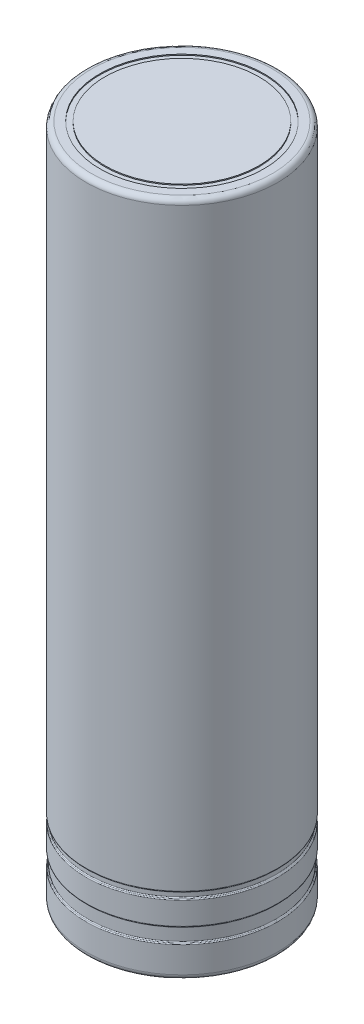
SolidWorks part; units mm, degrees
ref_plane "Front Plane" through (0, 0, 0) normal (0, 0, 1) x (1, 0, 0)
ref_plane "Top Plane" through (0, 0, 0) normal (0, 1, 0) x (1, 0, 0)
ref_plane "Right Plane" through (0, 0, 0) normal (1, 0, 0) x (0, 0, -1)
ref_axis "Y" through (0, 68.25, 0) along (0, -1, 0)
sketch "Sketch1" plane through (0, 0, 0) normal (0, 0, 1) x (1, 0, 0)
  line L0 (0, -32.5) -> (0, -39.9) construction
  line L1 (9.2, 25.04) -> (9.2, -32)
  line L4 (9.06, 25.6092) -> (9.06, 25.2308)
  line L6 (9.2, 27.96) -> (9.2, 25.8)
  line L8 (9.06, 29.3092) -> (9.06, 28.1508)
  line L9 (9.2, 32) -> (9.2, 29.5)
  line L12 (8.7, 32.5) -> (6.8, 32.5)
  line L14 (6.8, 32.4) -> (6.8, 32.5)
  line L16 (6.8, 32.4) -> (5.35, 32.4)
  line L18 (5.35, 31.9) -> (5.35, 32.4)
  line L20 (5.35, 31.9) -> (4.63, 31.9)
  line L22 (4.63, 31.9) -> (4.63, 32.2)
  line L23 (4.33, 32.5) -> (0, 32.5)
  line L25 (8.7, -32.5) -> (7.9, -32.5)
  line L27 (7.4, -32.5) -> (7.4, -32.4)
  line L29 (7.9, -32.4) -> (7.4, -32.4)
  line L32 (0, -32.5) -> (7.4, -32.5)
  line L33 (7.9, -32.4) -> (7.9, -32.5)
  line L34 (0, 32.5) -> (0, -32.5)
  line L35 (9.06, 29.3092) -> (9.2, 29.5) construction
  line L36 (8.7, 32.4) -> (6.8, 32.4)
  line L37 (9.1, 32) -> (9.1, 29.5)
  line L38 (8.96, 29.3092) -> (8.96, 28.1508)
  line L39 (9.1, 27.96) -> (9.1, 25.8)
  line L40 (8.96, 25.6092) -> (8.96, 25.2308)
  line L41 (9.1, 25.04) -> (9.1, -32)
  line L42 (8.7, -32.4) -> (7.9, -32.4)
  arc A1 (9.2, 25.04) -> (9.13, 25.1354) centre (9.1, 25.04) ccw
  arc A2 (9.06, 25.2308) -> (9.13, 25.1354) centre (9.16, 25.2308) ccw
  arc A4 (9.13, 25.7046) -> (9.06, 25.6092) centre (9.16, 25.6092) ccw
  arc A6 (9.13, 25.7046) -> (9.2, 25.8) centre (9.1, 25.8) ccw
  arc A9 (9.2, 27.96) -> (9.13, 28.0554) centre (9.1, 27.96) ccw
  arc A10 (9.06, 28.1508) -> (9.13, 28.0554) centre (9.16, 28.1508) ccw
  arc A13 (9.13, 29.4046) -> (9.06, 29.3092) centre (9.16, 29.3092) ccw
  arc A15 (9.13, 29.4046) -> (9.2, 29.5) centre (9.1, 29.5) ccw
  arc A17 (9.2, 32) -> (8.7, 32.5) centre (8.7, 32) ccw
  arc A19 (4.63, 32.2) -> (4.33, 32.5) centre (4.33, 32.2) ccw
  arc A21 (8.7, -32.5) -> (9.2, -32) centre (8.7, -32) ccw
  arc A22 (9.1, 32) -> (8.7, 32.4) centre (8.7, 32) ccw
  arc A23 (9.1, 29.5) -> (8.96, 29.3092) centre (9.16, 29.3092) ccw
  arc A24 (8.96, 28.1508) -> (9.1, 27.96) centre (9.16, 28.1508) ccw
  arc A25 (9.1, 25.8) -> (8.96, 25.6092) centre (9.16, 25.6092) ccw
  arc A26 (8.96, 25.2308) -> (9.1, 25.04) centre (9.16, 25.2308) ccw
  arc A27 (8.7, -32.4) -> (9.1, -32) centre (8.7, -32) ccw
  point P0 (7.9, -32.45)
  point P3 (3.7, -32.5)
  dimension "D1" = 0.5
  dimension "D3" = 0.5
  dimension "D4" = 0.3
  dimension "D5" = 0.1
  dimension "D2" = 65
  dimension "D6" = 18.4
  dimension "D7" = 0.5
  dimension "D8" = 0.1
  dimension "D9" = 14.8
  dimension "D10" = 9.26
  dimension "D11" = 10.7
  dimension "D12" = 0.1
  dimension "D13" = 0.6
  dimension "D14" = 13.6
  dimension "D15" = 0.14
  dimension "D16" = 1.54
  dimension "D17" = 0.76
  dimension "D18" = 6.7
  dimension "D19" = 3
  dimension "D20" = 0.1
  dimension "D21" = 0.1
revolve "Revolve1" add sketch "Sketch1" angle 360 about L0 region at (4.5442, -0.0497, 0)
revolve "Revolve2" add sketch "Sketch1<3>" angle 360 about L0 region at (9.135, -3.48, 0)
sketch "Sketch1<3>" plane through (0, 0, 0) normal (0, 0, 1) x (1, 0, 0) same geometry as "Sketch1"
sketch "Sketch2" plane through (0, 0, 0) normal (1, 0, 0) x (0, 0, -1)
  line L1 (8.7, -32.4) -> (-8.7, -32.4) construction
  line L5 (-8.7, -32.5) -> (8.7, -32.5) construction
  line B0 (-0.2, 21.7) -> (-0.2, 22.9866)
  line B1 (-0.2, 21.7) -> (0.2, 21.7) construction
  line B2 (-0.2, 21.7) -> (-0.2, 21.3) construction
  line B3 (-0.2, 21.3) -> (0.2, 21.3) construction
  line B4 (0.2, 21.7) -> (0.2, 21.3) construction
  line B5 (-0.2, 21.7) -> (0.2, 21.3) construction
  line B6 (-0.2, 21.3) -> (0.2, 21.7) construction
  line B7 (-0.2, 22.9866) -> (0.2, 22.9866)
  line B8 (0.2, 22.9866) -> (0.2, 21.7)
  line B9 (0.2, 21.3) -> (1.4866, 21.3)
  line B10 (1.4866, 21.3) -> (1.4866, 21.7)
  line B11 (1.4866, 21.7) -> (0.2, 21.7)
  line B12 (-0.2, 21.7) -> (-1.4866, 21.7)
  line B13 (-1.4866, 21.7) -> (-1.4866, 21.3)
  line B14 (-1.4866, 21.3) -> (-0.2, 21.3)
  line B15 (-0.2, 20.0134) -> (0.2, 20.0134)
  line B16 (0.2, 20.0134) -> (0.2, 21.3)
  line B17 (-0.2, 21.3) -> (-0.2, 20.0134)
  circle B18 centre (0, 21.5) radius 2
  circle B19 centre (0, 21.5) radius 1.8
  circle B20 centre (0, 21.5) radius 1.5 construction
  line B21 (-0.2, -28.2) -> (-0.2, -26.9134) construction
  line B22 (-0.2, -28.2) -> (0.2, -28.2)
  line B23 (-0.2, -28.2) -> (-0.2, -28.6) construction
  line B24 (-0.2, -28.6) -> (0.2, -28.6)
  line B25 (0.2, -28.2) -> (0.2, -28.6) construction
  line B26 (-0.2, -28.2) -> (0.2, -28.6) construction
  line B27 (-0.2, -28.6) -> (0.2, -28.2) construction
  line B28 (-0.2, -26.9134) -> (0.2, -26.9134) construction
  line B29 (0.2, -26.9134) -> (0.2, -28.2) construction
  line B30 (0.2, -28.6) -> (1.4866, -28.6)
  line B31 (1.4866, -28.6) -> (1.4866, -28.2)
  line B32 (1.4866, -28.2) -> (0.2, -28.2)
  line B33 (-0.2, -28.2) -> (-1.4866, -28.2)
  line B34 (-1.4866, -28.2) -> (-1.4866, -28.6)
  line B35 (-1.4866, -28.6) -> (-0.2, -28.6)
  line B36 (-0.2, -29.8866) -> (0.2, -29.8866) construction
  line B37 (0.2, -29.8866) -> (0.2, -28.6) construction
  line B38 (-0.2, -28.6) -> (-0.2, -29.8866) construction
  circle B39 centre (0, -28.4) radius 2
  circle B40 centre (0, -28.4) radius 1.8
  circle B41 centre (0, -28.4) radius 1.5 construction
  dimension "D1" = 4
  dimension "D2" = 54
sketch_block_instance "Plus_Sign-1"
sketch_block "Plus_Sign" parameters "D2"=2, "D1"=1.8, "D3"=1.65, "D4"=0.2
sketch_block_instance "Minus_Sign-1"
sketch_block "Minus_Sign" parameters "D1"=2, "D2"=1.65, "D3"=0.2, "D4"=0.1
split line "Split Line1"
move or copy body "Body-Move/Copy1" bodies to move or copy 111 113 copy no rotation origin (0, 0, 0) rotation axis (0, 0, 1) rotation angle 180
